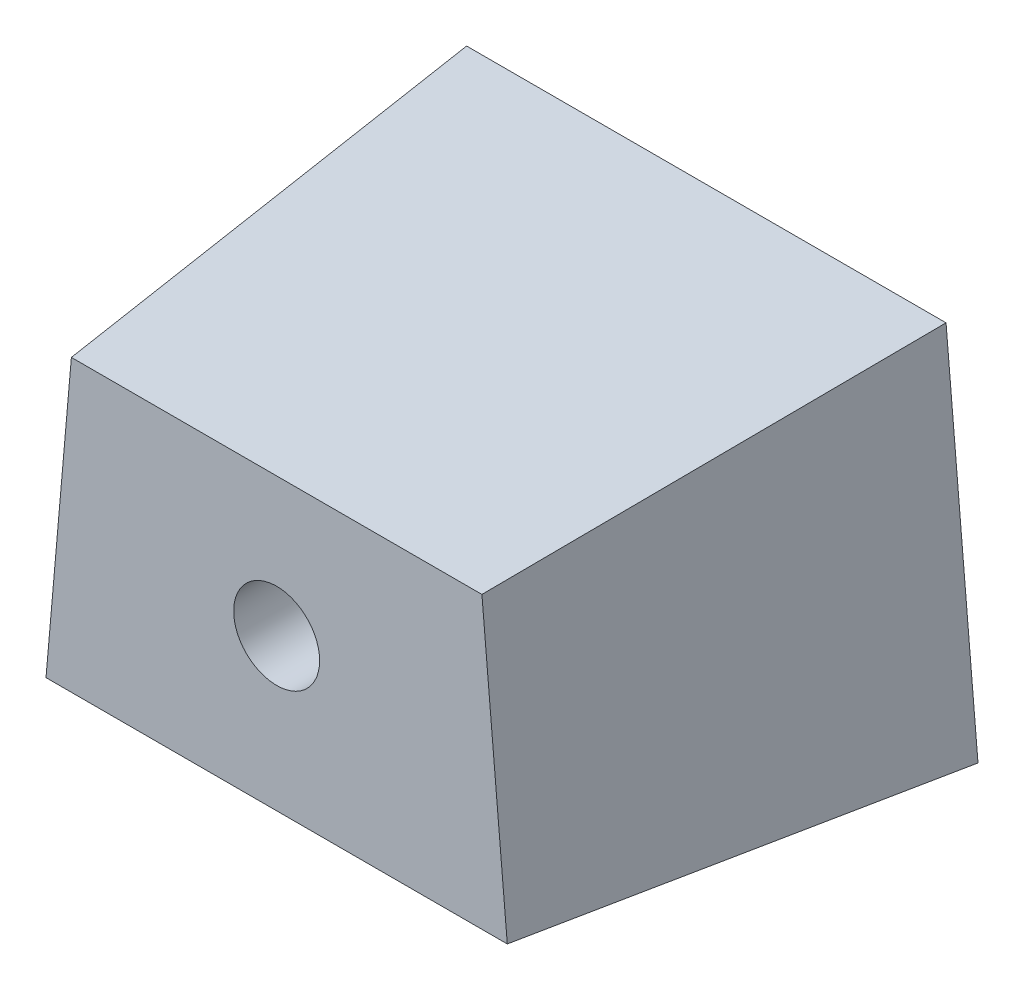
SolidWorks part; units mm, degrees
ref_plane "Ön Düzlem" through (0, 0, 0) normal (0, 0, 1) x (1, 0, 0)
ref_plane "Üst Düzlem" through (0, 0, 0) normal (0, 1, 0) x (1, 0, 0)
ref_plane "Sağ Düzlem" through (0, 0, 0) normal (1, 0, 0) x (0, 0, -1)
sketch "Çizim1" plane through (0, 0, 0) normal (0, 0, 1) x (1, 0, 0)
  line L0 (-22, 20) -> (22, 20)
  line L5 (22, 20) -> (25.5, -20.0052)
  line L6 (25.5, -20.0052) -> (-25.5, -20.0052)
  line L7 (-25.5, -20.0052) -> (-22, 20)
  dimension "D1" = 44
  dimension "D2" = 51
  dimension "D3" = 95
  dimension "D4" = 95
  dimension "D5" = 40.0052
  dimension "D6" = 85
  dimension "D7" = 85
  dimension "D8" = 22
  dimension "D9" = 20
  dimension "D10" = 40.158
  dimension "D11" = 40.158
extrude "Yükseklik-Ekstrüzyon1" add sketch "Çizim1" along normal blind 40 draft 5
sketch "Çizim2" plane through (0, 0, 40) normal (0, 0, 1) x (1, 0, 0)
  circle A0 centre (0, 0) radius 4
  dimension "D1" = 8
extrude "Kes-Ekstrüzyon1" cut sketch "Çizim2" against normal blind 8
sketch "Çizim3" plane through (0, 0, 0) normal (0, 0, -1) x (-1, 0, 0)
  line L0 (22.3155, 16.3935) -> (-22.3155, 16.3935)
  line L1 (22, 20) -> (25.5, -20.0052) construction
  line L2 (-25.5, -20.0052) -> (-22, 20) construction
  line L3 (25.2901, -17.6065) -> (-25.2901, -17.6065)
  line L4 (-25.0779, 19.3935) -> (24.9221, 19.3935) construction
  line L7 (22.3155, 16.3935) -> (22, 20)
  line L8 (22, 20) -> (-22, 20)
  line L9 (-22, 20) -> (-22.3155, 16.3935)
  line L10 (25.2901, -17.6065) -> (25.5, -20.0052)
  line L11 (25.5, -20.0052) -> (-25.5, -20.0052)
  line L12 (-25.5, -20.0052) -> (-25.2901, -17.6065)
  dimension "D1" = 3
  dimension "D2" = 34
extrude "Kes-Ekstrüzyon2" cut sketch "Çizim3" against normal blind 50 draft 5 draft outward yes
sketch "Çizim4" plane through (0, 0, 0) normal (0, 0, -1) x (-1, 0, 0)
  circle A0 centre (0, 0) radius 4
  dimension "D1" = 8
extrude "Kes-Ekstrüzyon3" cut sketch "Çizim4" against normal blind 5
